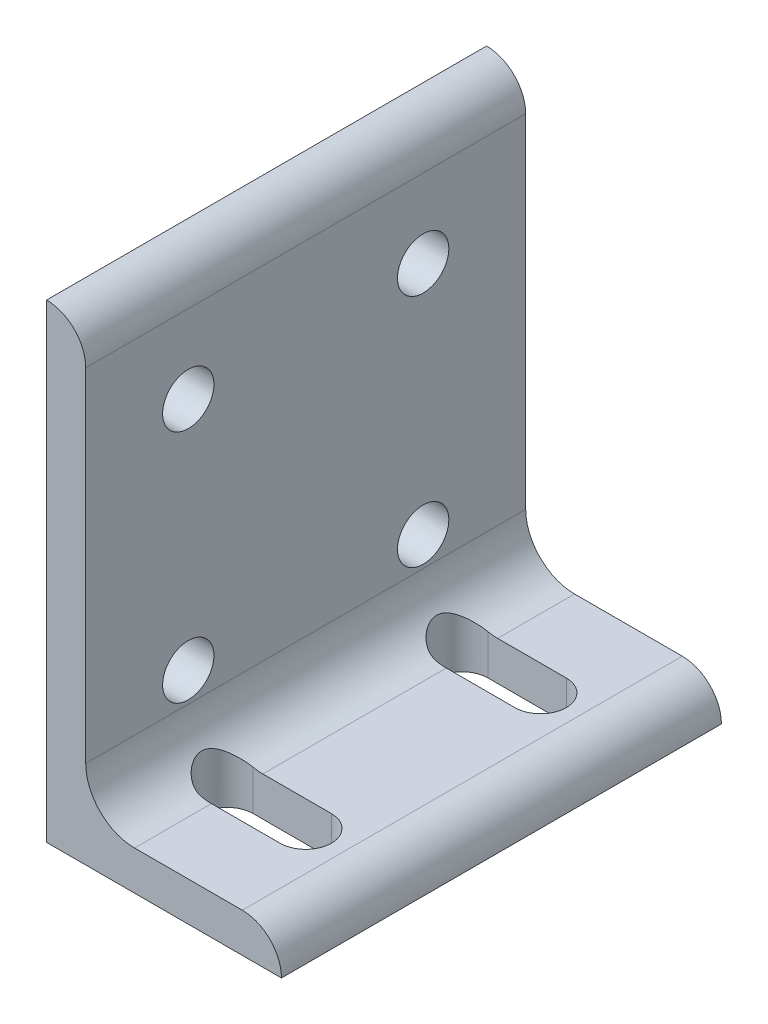
SolidWorks part; units mm, degrees
material "6105-T5 Aluminum"
ref_plane "Front Plane" through (0, 0, 0) normal (0, 0, 1) x (1, 0, 0)
ref_plane "Top Plane" through (0, 0, 0) normal (0, 1, 0) x (1, 0, 0)
ref_plane "Right Plane" through (0, 0, 0) normal (1, 0, 0) x (0, 0, -1)
sketch "Sketch2" plane through (0, 0, 0) normal (0, 0, 1) x (1, 0, 0)
  line L0 (0, 0) -> (0, 76.2)
  line L1 (38.1, 6.35) -> (38.1, 0)
  line L2 (6.35, 76.2) -> (6.35, 14.2748)
  line L3 (14.2748, 6.35) -> (38.1, 6.35)
  line L4 (0, 76.2) -> (6.35, 76.2)
  line L5 (38.1, 0) -> (0, 0)
  arc A2 (6.35, 14.2748) -> (14.2748, 6.35) centre (14.2748, 14.2748) ccw
  dimension "D3" = 76.2
  dimension "D4" = 7.9248
  dimension "D1" = 6.35
  dimension "D2" = 6.35
  dimension "D5" = 38.1
extrude "Boss-Extrude1" add sketch "Sketch2" along normal mid plane 71.374
fillet "Fillet1" radius 6.35 2 edges at (38.1, 6.35, 0) (6.35, 76.2, 0)
sketch "Sketch3" plane through (0, 0, 0) normal (0, -1, 0) x (1, 0, 0)
  line L0 (25.4, 19.05) -> (12.7, 19.05) construction
  line L1 (25.4, 14.8844) -> (12.7, 14.8844)
  line L2 (25.4, 23.2156) -> (12.7, 23.2156)
  line L3 (25.4, -19.05) -> (12.7, -19.05) construction
  line L4 (25.4, -23.2156) -> (12.7, -23.2156)
  line L5 (25.4, -14.8844) -> (12.7, -14.8844)
  line L6 (0, 35.687) -> (0, -35.687) construction
  arc A0 (25.4, 14.8844) -> (25.4, 23.2156) centre (25.4, 19.05) ccw
  arc A1 (12.7, 23.2156) -> (12.7, 14.8844) centre (12.7, 19.05) ccw
  arc A2 (25.4, -23.2156) -> (25.4, -14.8844) centre (25.4, -19.05) ccw
  arc A3 (12.7, -14.8844) -> (12.7, -23.2156) centre (12.7, -19.05) ccw
  point P2 (19.05, 19.05)
  point P7 (19.05, -19.05)
  dimension "D3" = 4.1656
  dimension "D1" = 12.7
  dimension "D2" = 25.4
  dimension "D4" = 38.1
  dimension "D5" = 19.05
extrude "Cut-Extrude1" cut sketch "Sketch3" against normal up to next
sketch "Sketch4" plane through (0, 0, 0) normal (-1, 0, 0) x (0, 0, 1)
  line L1 (19.05, 19.05) -> (19.05, 57.15) construction
  line L2 (0, 27.9248) -> (0, 53.4331) construction
  circle A0 centre (19.05, 57.15) radius 4.1656
  circle A1 centre (-19.05, 19.05) radius 4.1656
  circle A2 centre (-19.05, 57.15) radius 4.1656
  circle A3 centre (19.05, 19.05) radius 4.1656
  dimension "D7" = 8.3312
  dimension "D3" = 38.1
  dimension "D1" = 19.05
  dimension "D2" = 19.05
extrude "Cut-Extrude2" cut sketch "Sketch4" against normal through all
